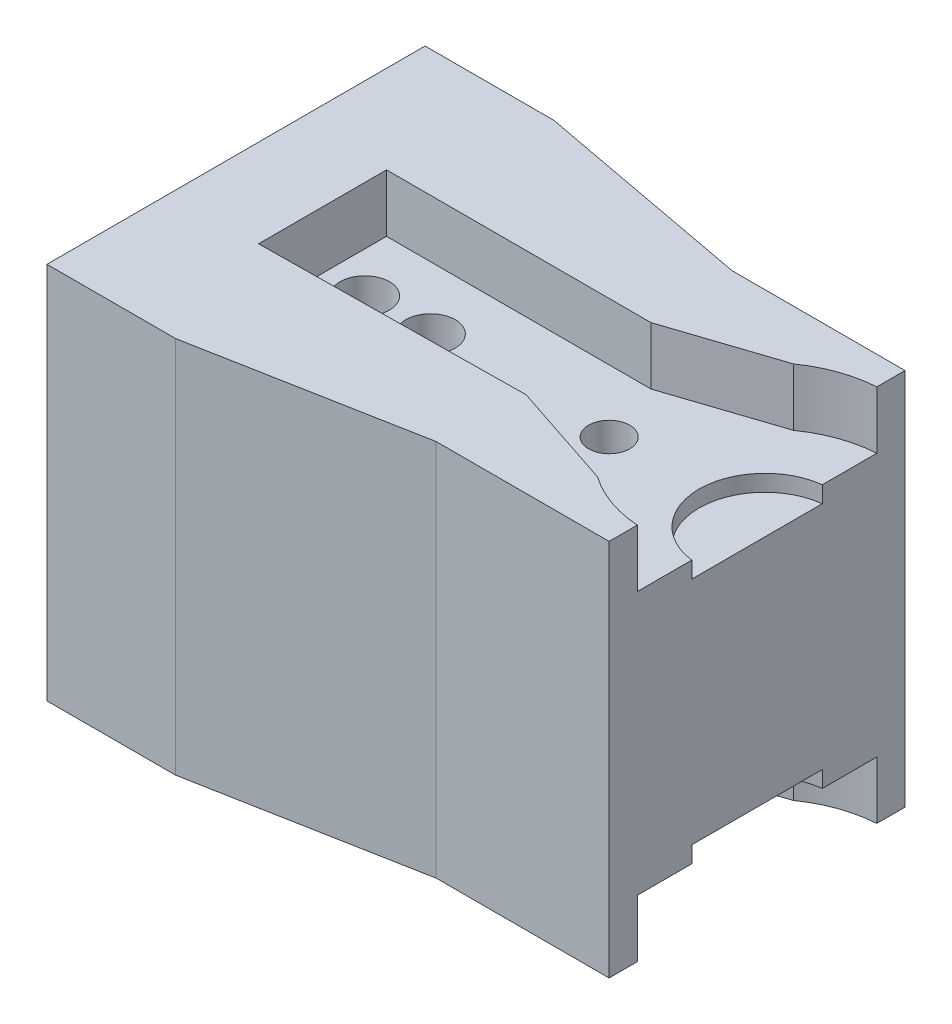
SolidWorks part; units mm, degrees
ref_plane "Front Plane" through (0, 0, 0) normal (0, 0, 1) x (1, 0, 0)
ref_plane "Top Plane" through (0, 0, 0) normal (0, 1, 0) x (1, 0, 0)
ref_plane "Right Plane" through (0, 0, 0) normal (1, 0, 0) x (0, 0, -1)
sketch "Sketch1" plane through (0, 0, 0) normal (0, 1, 0) x (1, 0, 0)
  line L0 (0, 0) -> (14.6038, 0) construction
  line L1 (14.6038, 0) -> (-20.0982, 0) construction
  line L2 (14.6038, -7.2) -> (14.6038, 7.2) construction
  line L3 (-661.2792, -270.937) -> (-113.9458, -270.937) construction
  line L4 (3.082, 5.9567) -> (3.082, -8.253) construction
  line L5 (-17.0385, 7.2) -> (-17.0385, 4.8714) construction
  line L6 (-13.0385, 7.2) -> (-13.0385, 4.8714) construction
  line L7 (6.8243, 9.0002) -> (6.8243, -9.0002)
  line L8 (6.8276, 9.1929) -> (-2.1724, 9.1929) construction
  line L9 (-24.868, 11.5) -> (-24.868, -11.5)
  line L10 (-3.4224, -3.8) -> (-3.4224, 3.8) construction
  line L11 (6.8243, 0.0002) -> (6.8243, 9.0002) construction
  line L12 (6.8243, 0.0002) -> (6.8243, -9.0002) construction
  line L15 (-3.4224, 3.8) -> (3.082, 5.9567)
  line L16 (-3.4224, -3.8) -> (3.082, -5.9567)
  line L17 (-3.4224, 3.8) -> (-19.5134, 3.8)
  line L18 (-19.5134, 3.8) -> (-19.5134, -3.9825)
  line L19 (-17.0385, 11.5) -> (-24.868, 11.5)
  line L20 (-19.5134, -3.9825) -> (-3.4224, -3.8)
  line L21 (6.8243, 9.0002) -> (-3.6905, 9.0002)
  line L22 (6.8243, -9.0002) -> (-3.6905, -9.0002)
  line L23 (-17.0385, -11.5) -> (-17.0385, 11.5) construction
  line L27 (-3.6905, 9.0002) -> (-17.0385, 11.5)
  line L28 (-3.6905, -9.0002) -> (-17.0385, -11.5)
  line L30 (-24.868, -11.5) -> (-17.0385, -11.5)
  arc A0 (6.8243, 3.9714) -> (6.8243, -3.9714) centre (7.3019, 0) ccw
  circle A1 centre (-17.0385, 0) radius 1.5
  circle A2 centre (-13.0385, 0) radius 1.5
  circle A3 centre (-2.1724, 0) radius 1.25
  arc A4 (6.8243, 7.2844) -> (3.082, 5.9567) centre (7.3019, 0) ccw
  arc A5 (3.082, -5.9567) -> (6.8243, -7.2844) centre (7.3019, 0) ccw
  point P8 (0, 0)
  point P17 (-17.0385, 6.0357)
  point P25 (3.082, -5.9567)
  point P26 (0, 0)
  point P35 (-17.0772, 11.5)
  point P39 (-3.4224, 0)
  point P41 (-3.4224, 0)
  point P43 (0, 0)
  point P44 (6.826, 0)
  dimension "D4" = 8
  dimension "D5" = 3
  dimension "D7" = 3
  dimension "D10" = 2.5
  dimension "D11" = 14.6
  dimension "D2" = 14.4
  dimension "D6" = 4
  dimension "D8" = 9
  dimension "D12" = 9
  dimension "D13" = 3.8
extrude "Boss-Extrude1" add sketch "Sketch1" along normal mid plane 23 contours A5 L16 L20 L18 L17 L15 A4 L7 L21 L27 L19 L9 L30 L28 L22 region at (6.4327, 0, -8.1423)
extrude "Boss-Extrude2" add sketch "Sketch1<13>" along normal mid plane 16 contours L16 A5 L7 A0 A4 L15 L17 L18 L20 A3 A2 A1 region at (-5.3254, 0, 0.0287)
sketch "Sketch1<13>" plane through (0, 0, 0) normal (0, 1, 0) x (1, 0, 0) same geometry as "Sketch1"
extrude "Boss-Extrude3" add sketch "Sketch1<14>" along normal mid plane 14 contours L7 A0 region at (5.3434, 0, 0)
sketch "Sketch1<14>" plane through (0, 0, 0) normal (0, 1, 0) x (1, 0, 0) same geometry as "Sketch1"
